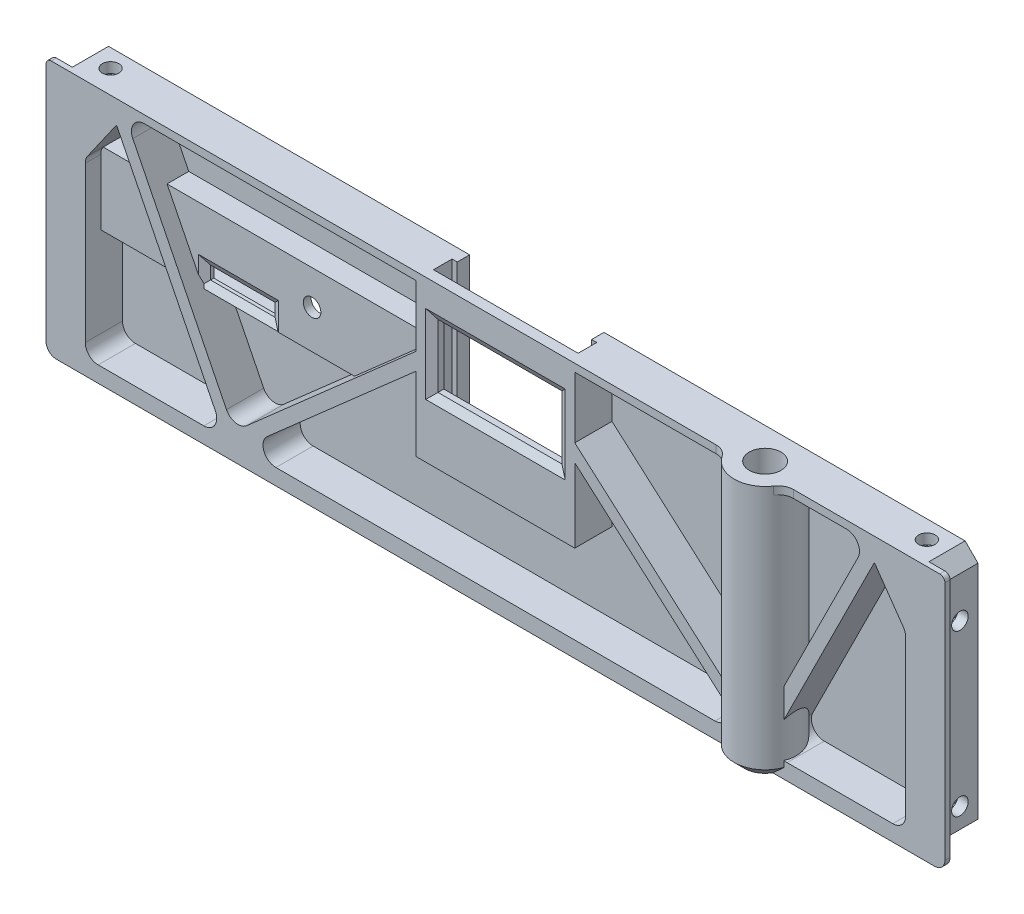
SolidWorks part; units mm, degrees
ref_plane "Front Plane" through (0, 0, 0) normal (0, 0, 1) x (1, 0, 0)
ref_plane "Top Plane" through (0, 0, 0) normal (0, 1, 0) x (1, 0, 0)
ref_plane "Right Plane" through (0, 0, 0) normal (1, 0, 0) x (0, 0, -1)
sketch "Sketch1" plane through (0, 0, 0) normal (0, 0, 1) x (1, 0, 0)
  line L1 (87, -25.55) -> (-87, -25.55)
  line L2 (87, -25.55) -> (87, 25.55)
  line L3 (87, 25.55) -> (-87, 25.55)
  line L4 (-87, -25.55) -> (-87, 25.55)
  line L5 (87, -25.55) -> (-87, 25.55) construction
  line L6 (87, 25.55) -> (-87, -25.55) construction
  point P0 (0, 0)
  dimension "D1" = 174
  dimension "D2" = 51.1
extrude "Boss-Extrude1" add sketch "Sketch1" against normal blind 8
sketch "Sketch2" plane through (0, 0, -8) normal (0, 0, -1) x (-1, 0, 0)
  line L5 (-87, -25.55) -> (-87, 25.55) construction
  line L6 (-87, 25.55) -> (87, 25.55) construction
  line L13 (85.4, -23.95) -> (85.4, 23.95)
  line L14 (-85.4, -23.95) -> (85.4, -23.95)
  line L15 (-85.4, 23.95) -> (-85.4, -23.95)
  line L16 (85.4, 23.95) -> (-85.4, 23.95)
  point P2 (0, 23.95)
  point P5 (85.4, 0)
  dimension "D1" = 1.6
  dimension "D2" = 1.6
extrude "Cut-Extrude1" cut sketch "Sketch2" against normal offset from surface (7 mm away) 1 flip side to cut up to face at (0, 0, 0)
chamfer "Chamfer1" distance 2.5 angle 45 4 edges at (-85.4, -23.95, -4.5) (-85.4, 23.95, -4.5) (85.4, -23.95, -4.5) (85.4, 23.95, -4.5)
fillet "Fillet1" radius 2 2 edges at (-87, -25.55, -0.5) (87, -25.55, -0.5)
sketch "Sketch3" plane through (0, 0, 0) normal (0, 0, 1) x (1, 0, 0)
  line L1 (-82.9, 23.95) -> (-85.4, 21.45) construction
  line L2 (-82.9, 23.95) -> (82.9, 23.95) construction
  line L3 (-82.9, 23.95) -> (-85.4, 21.45) construction
  line L4 (-82.9, 23.95) -> (82.9, 23.95) construction
  line L5 (85.4, 21.45) -> (82.9, 23.95) construction
  line L6 (85.4, 21.45) -> (85.4, -21.45) construction
  line L7 (82.9, -23.95) -> (85.4, -21.45) construction
  line L8 (82.9, -23.95) -> (-82.9, -23.95) construction
  line L9 (-85.4, -21.45) -> (-82.9, -23.95) construction
  line L10 (-85.4, -21.45) -> (-85.4, 21.45) construction
  line L11 (85.4, 21.45) -> (82.9, 23.95) construction
  line L12 (85.4, 21.45) -> (85.4, -21.45) construction
  line L13 (82.9, -23.95) -> (85.4, -21.45) construction
  line L14 (82.9, -23.95) -> (-82.9, -23.95) construction
  line L15 (-85.4, -21.45) -> (-82.9, -23.95) construction
  line L16 (-85.4, -21.45) -> (-85.4, 21.45) construction
  line L26 (79.4, -22.45) -> (-79.4, -22.45)
  line L27 (79.4, -22.45) -> (79.4, 22.45)
  line L28 (79.4, 22.45) -> (-79.4, 22.45)
  line L29 (-79.4, -22.45) -> (-79.4, 22.45)
  line L30 (79.4, -22.45) -> (-79.4, 22.45) construction
  line L31 (79.4, 22.45) -> (-79.4, -22.45) construction
  point P4 (0, 0)
  dimension "D1" = 3
  dimension "D2" = 6
extrude "Cut-Extrude2" cut sketch "Sketch3" against normal offset from surface (7.2 mm away) 0.8 up to face at (0, 0, -8)
sketch "Sketch9" plane through (0, 0, 0) normal (0, 0, 1) x (1, 0, 0)
  line L0 (-73.4, 22.45) -> (-73.4, 19.45)
  line L1 (-79.4, 22.45) -> (79.4, 22.45) construction
  line L2 (-73.4, 19.45) -> (-79.4, 10.8811)
  line L3 (-79.4, -22.45) -> (-79.4, 22.45) construction
  line L4 (-79.4, 10.8811) -> (-79.4, 22.45)
  line L5 (-79.4, 22.45) -> (-73.4, 22.45)
  dimension "D1" = 6
  dimension "D2" = 35
  dimension "D3" = 3
extrude "Boss-Extrude2" add sketch "Sketch9" against normal up to surface (7.2 mm away) up to face at (0, 0, -7.2)
hole_wizard "Ø3.0mm Dowel Hole1" positions "Sketch4" profile "Sketch5" hole size "Ø3.0" standard "ANSI Metric"
sketch "Sketch4" plane through (-85.4, 0, 0) normal (-1, 0, 0) x (0, 0, 1)
  line L0 (-4.5, 13.55) -> (-4.5, -17.55) construction
  line L2 (-8, -21.45) -> (-8, 21.45) construction
  line L4 (0, -25.55) -> (-1, -25.55) construction
  line L5 (-1, 25.55) -> (0, 25.55) construction
  point P0 (-4.5, 13.55)
  point P3 (-4.5, -17.55)
  dimension "D1" = 3.5
  dimension "D2" = 12
  dimension "D3" = 8
sketch "Sketch5" plane through (-85.4, 13.55, -4.5) normal (0, 1, 0) x (0, 0, 1)
  line L0 (0, 0) -> (0, 5)
  line L1 (0, 5) -> (1.6, 5)
  line L2 (1.6, 5) -> (1.6, 0)
  line L5 (1.6, 0) -> (0, 0)
  line L10 (0, 5) -> (-1.6, 5) construction
  line L11 (0, -6.35) -> (0, 107.95) construction
  dimension "Hole Dia." = 3.2
  dimension "Hole Depth" = 5
  dimension "Drill Angle" = 180
hole_wizard "Ø3.0mm Dowel Hole2" positions "Sketch7" profile "Sketch8" hole size "Ø3.0" standard "ANSI Metric"
sketch "Sketch7" plane through (0, 23.95, 0) normal (0, 1, 0) x (1, 0, 0)
  line L0 (-82.9, 8) -> (82.9, 8) construction
  line L2 (-87, 1) -> (-87, 0) construction
  point P0 (-79, 4.5)
  dimension "D1" = 3.5
  dimension "D2" = 8
sketch "Sketch8" plane through (-79, 23.95, -4.5) normal (1, 0, 0) x (0, 0, 1)
  line L0 (0, 0) -> (0, 5)
  line L1 (0, 5) -> (1.6, 5)
  line L2 (1.6, 5) -> (1.6, 0)
  line L5 (1.6, 0) -> (0, 0)
  line L10 (0, 5) -> (-1.6, 5) construction
  line L11 (0, -6.35) -> (0, 107.95) construction
  dimension "Hole Dia." = 3.2
  dimension "Hole Depth" = 5
  dimension "Drill Angle" = 180
sketch "Sketch10" plane through (-85.4, 0, 0) normal (-1, 0, 0) x (0, 0, 1)
  line L0 (-8, -21.45) -> (-8, 21.45) construction
  line L1 (-8, 16.3) -> (-1.75, 16.3)
  line L2 (-8, 16.3) -> (-8, 10.8)
  line L3 (-8, 10.8) -> (-1.75, 10.8)
  line L4 (-1.75, 16.3) -> (-1.75, 10.8)
  line L6 (-8, -14.8) -> (-1.75, -14.8)
  line L7 (-8, -14.8) -> (-8, -20.3)
  line L8 (-8, -20.3) -> (-1.75, -20.3)
  line L9 (-1.75, -14.8) -> (-1.75, -20.3)
  point P6 (-1.75, -17.55)
  point P8 (-1.75, 13.55)
  dimension "D1" = 5.5
  dimension "D2" = 2.75
extrude "Cut-Extrude3" cut sketch "Sketch10" against normal blind 1.8 from offset 2 offset against normal yes
sketch "Sketch11" plane through (0, 23.95, 0) normal (0, 1, 0) x (1, 0, 0)
  line L0 (-82.9, 8) -> (82.9, 8) construction
  line L1 (-81.75, 8) -> (-76.25, 8)
  line L2 (-81.75, 8) -> (-81.75, 1.75)
  line L3 (-81.75, 1.75) -> (-76.25, 1.75)
  line L4 (-76.25, 8) -> (-76.25, 1.75)
  point P6 (-79, 1.75)
  dimension "D1" = 5.5
  dimension "D2" = 2.75
extrude "Cut-Extrude4" cut sketch "Sketch11" against normal blind 1.8 from offset 2 offset against normal yes
mirror "Mirror1" about plane through (0, 0, 0) normal (1, 0, 0) of "Cut-Extrude4", "Cut-Extrude3", "Ø3.0mm Dowel Hole2", "Ø3.0mm Dowel Hole1", "Boss-Extrude2"
sketch "Sketch12" plane through (0, 0, -7.2) normal (0, 0, 1) x (1, 0, 0)
  line L0 (-73.4, 22.45) -> (-51.0137, -22.45) construction
  line L1 (-79.4, -22.45) -> (79.4, -22.45) construction
  line L2 (-51.0137, -22.45) -> (0, 22.45) construction
  line L3 (73.4, 22.45) -> (-73.4, 22.45) construction
  line L4 (0, 22.45) -> (51.0137, -22.45) construction
  line L5 (51.0137, -22.45) -> (73.4, 22.45) construction
  line L6 (-74.5187, 21.8923) -> (-51.9874, -23.2985)
  line L7 (-50.4317, -23.603) -> (0, 20.7848)
  line L8 (0, 20.7848) -> (50.4317, -23.603)
  line L9 (51.9874, -23.2985) -> (74.5187, 21.8923)
  line L10 (-72.2813, 23.0077) -> (-50.62, -20.4382)
  line L11 (-50.62, -20.4382) -> (-0.6607, 23.5337)
  line L12 (0.6607, 23.5337) -> (50.62, -20.4382)
  line L13 (50.62, -20.4382) -> (72.2813, 23.0077)
  line L14 (0, 20.7848) -> (51.4074, -24.4618) construction
  line L15 (51.4074, -24.4618) -> (74.5187, 21.8923) construction
  line L16 (-50.62, -20.4382) -> (0, 24.1152) construction
  line L17 (0, 24.1152) -> (50.62, -20.4382) construction
  line L18 (-74.5187, 21.8923) -> (-51.4074, -24.4618) construction
  line L19 (-51.4074, -24.4618) -> (0, 20.7848) construction
  line L20 (79.4, -22.45) -> (-79.4, -22.45) construction
  line L21 (-79.4, -22.45) -> (-79.4, 10.8811) construction
  arc A0 (-74.5187, 21.8923) -> (-72.2813, 23.0077) centre (-73.4, 22.45) cw
  arc A1 (74.5187, 21.8923) -> (72.2813, 23.0077) centre (73.4, 22.45) ccw
  arc A2 (50.4317, -23.603) -> (51.9874, -23.2985) centre (51.0924, -22.8524) ccw
  arc A3 (-0.6607, 23.5337) -> (0.6607, 23.5337) centre (0, 22.783) cw
  arc A4 (-51.9874, -23.2985) -> (-50.4317, -23.603) centre (-51.0924, -22.8524) ccw
  dimension "D3" = 1
  dimension "D1" = 1.25
  dimension "D2" = 26.5
extrude "Boss-Extrude3" add sketch "Sketch12" along normal up to surface (7.2 mm away) up to face at (0, 7.5828, 0)
sketch "Sketch13" plane through (0, 0, 0) normal (0, 0, 1) x (1, 0, 0)
  line L0 (-73.4, 19.45) -> (-73.4, 19.6486)
  line L1 (-73.4, 19.6486) -> (-73.301, 19.45)
  line L2 (-73.4, 19.6486) -> (-52.4104, -22.45) construction
  line L3 (-73.301, 19.45) -> (-73.4, 19.45)
  line L4 (0, 0) -> (0, 25.4565) construction
  line L5 (73.301, 19.45) -> (73.4, 19.45)
  line L6 (73.4, 19.6486) -> (73.301, 19.45)
  line L7 (73.4, 19.45) -> (73.4, 19.6486)
extrude "Small Fix" add sketch "Sketch13" against normal up to surface (7.2 mm away) up to face at (-71.6021, 1.0159, -7.2)
fillet "Fillet2" radius 2.5 15 edges at (79.4, -22.45, -3.6) (79.4, 10.8811, -3.6) (52.4104, -22.45, -3.6) (72.0032, 22.45, -3.6) (50.62, -20.4382, -3.6) (1.892, 22.45, -3.6) (49.1217, -22.45, -3.6) (0, 20.7848, -3.6) (-49.1217, -22.45, -3.6) (-1.892, 22.45, -3.6) (-50.62, -20.4382, -3.6) (-72.0032, 22.45, -3.6) (-79.4, 10.8811, -3.6) (-79.4, -22.45, -3.6) (-52.4104, -22.45, -3.6)
fillet "Fillet3" radius 0.1 4 edges at (73.4, 19.45, -3.6) (73.301, 19.45, -3.6) (-73.301, 19.45, -3.6) (-73.4, 19.45, -3.6)
sketch "Sketch14" plane through (0, 0, -8) normal (0, 0, -1) x (-1, 0, 0)
  line L1 (-13.85, 22.45) -> (13.85, 22.45) construction
  line L2 (-13.85, 22.45) -> (-13.85, -5.55) construction
  line L3 (-13.85, -5.55) -> (13.85, -5.55) construction
  line L4 (13.85, 22.45) -> (13.85, -5.55) construction
  line L5 (82.9, 23.95) -> (-82.9, 23.95) construction
  line L6 (-15.35, 23.95) -> (-15.35, -7.05)
  line L7 (-15.35, -7.05) -> (15.35, -7.05)
  line L8 (15.35, 23.95) -> (15.35, -7.05)
  line L9 (-15.35, 22.45) -> (-15.35, -7.05) construction
  line L10 (15.35, 22.45) -> (15.35, -7.05) construction
  line L11 (-15.35, 23.95) -> (15.35, 23.95)
  point P6 (0, -5.55)
  dimension "D1" = 28
  dimension "D2" = 27.7
  dimension "D3" = 1.5
  dimension "D4" = 1.5
extrude "Boss-Extrude4" add sketch "Sketch14" against normal up to surface (8 mm away) up to face at (-42.2461, 7.7039, 0)
sketch "Sketch17" plane through (0, 23.95, 0) normal (0, 1, 0) x (1, 0, 0)
  line L0 (87, 0) -> (-87, 0) construction
  line L1 (-14, 5.6) -> (14, 5.6)
  line L2 (-14, 5.6) -> (-14, 2)
  line L3 (-14, 2) -> (14, 2)
  line L4 (14, 5.6) -> (14, 2)
  point P8 (0, 2)
  point P11 (-13.85, 8)
  dimension "D1" = 3.6
  dimension "D2" = 2
  dimension "D3" = 0.15
extrude "Cut-Extrude6" cut sketch "Sketch17" against normal up to vertex (29.5 mm away) up to point (13.85, -5.55, -8)
sketch "Sketch18" plane through (0, 0, -8) normal (0, 0, -1) x (-1, 0, 0)
  line L0 (82.9, 23.95) -> (-82.9, 23.95) construction
  line L1 (-13, 23.95) -> (13, 23.95)
  line L2 (-13, 23.95) -> (-13, -2.55)
  line L3 (-13, -2.55) -> (13, -2.55)
  line L4 (13, 23.95) -> (13, -2.55)
  line L5 (-14, -5.55) -> (14, -5.55) construction
  point P6 (0, -2.55)
  dimension "D1" = 26
  dimension "D2" = 3
extrude "Cut-Extrude7" cut sketch "Sketch18" against normal up to surface (6 mm away) up to face at (0, 9.2, -2)
sketch "Sketch19" plane through (0, 0, 0) normal (0, 0, 1) x (1, 0, 0)
  line L1 (-13, 18.2) -> (13, 18.2) construction
  line L2 (-13, 18.2) -> (-13, 3.95) construction
  line L3 (-13, 3.95) -> (13, 3.95) construction
  line L4 (13, 18.2) -> (13, 3.95) construction
  line L6 (-12, 17.2) -> (12, 17.2)
  line L7 (12, 17.2) -> (12, 4.95)
  line L8 (-12, 4.95) -> (12, 4.95)
  line L9 (-12, 17.2) -> (-12, 4.95)
  dimension "D1" = 1
extrude "Cut-Extrude8" cut sketch "Sketch19" against normal up to surface (2 mm away) up to face at (0, 9.2, -2)
chamfer "Chamfer2" distance 1.5 angle 30 4 edges at (0, 4.95, 0) (-12, 11.075, 0) (12, 11.075, 0) (0, 17.2, 0) first distance on face at (0, 11.075, 0)
sketch "Sketch21" plane through (0, 0, -1) normal (0, 0, -1) x (-1, 0, 0)
  line L0 (87, -23.55) -> (87, 25.55) construction
  line L1 (-87, 25.55) -> (87, 25.55)
  line L2 (-87, 25.55) -> (-87, 23.95)
  line L3 (-87, 23.95) -> (87, 23.95)
  line L4 (87, 25.55) -> (87, 23.95)
  line L5 (82.9, 23.95) -> (-82.9, 23.95) construction
extrude "Cut-Extrude10" cut sketch "Sketch21" against normal through all
sketch "Sketch22" plane through (0, 0, 0) normal (0, 0, 1) x (1, 0, 0)
  line L0 (-79.4, -2.55) -> (-30.296, -2.55)
  line L1 (-79.4, -2.55) -> (-79.4, 11.55)
  line L2 (-79.4, 11.55) -> (-23.6, 11.55)
  line L3 (-23.6, 3.3435) -> (-23.6, 11.55) construction
  line L4 (-81.6, 0.95) -> (-25.6, 0.95) construction
  line L5 (-81.6, 0.95) -> (-81.6, 2.55) construction
  line L6 (-81.6, 2.55) -> (-25.6, 2.55) construction
  line L7 (-25.6, 0.95) -> (-25.6, 2.55) construction
  line L9 (-30.296, -2.55) -> (-15.35, 10.6048)
  line L10 (-15.35, 11.55) -> (-23.6, 11.55)
  line L12 (-15.35, 10.6048) -> (-48.1808, -18.2914) construction
  line L14 (-79.4, 10.0929) -> (-79.4, -19.95) construction
  line L15 (82.9, -23.95) -> (-82.9, -23.95) construction
  line L16 (-87, 23.95) -> (-87, -23.55) construction
  line L17 (-15.35, 10.6048) -> (-15.35, 11.55)
  line L18 (-15.35, 22.45) -> (-15.35, 10.6048) construction
  line L19 (-15.35, 10.6048) -> (-48.1808, -18.2914) construction
  dimension "D1" = 9
  dimension "D2" = 2
  dimension "D3" = 56
  dimension "D4" = 1.6
  dimension "D5" = 24.9
  dimension "D6" = 5.4
  dimension "D7" = 3.5
extrude "Boss-Extrude5" add sketch "Sketch22" against normal up to surface (7.2 mm away) from offset 3 up to face at (-71.6654, -0.5445, -7.2) offset against normal yes
sketch "Sketch23" plane through (0, 0, -8) normal (0, 0, -1) x (-1, 0, 0)
  line L1 (24.1, 10.55) -> (83.1, 10.55)
  line L2 (24.1, 10.55) -> (24.1, 0.95)
  line L3 (24.1, 0.95) -> (83.1, 0.95)
  line L4 (83.1, 10.55) -> (83.1, 0.95)
  line L5 (81.6, 0.95) -> (25.6, 0.95) construction
  line L6 (81.6, 0.95) -> (81.6, 2.55) construction
  line L7 (79.4, 11.55) -> (23.6, 11.55) construction
  point P6 (53.6, 0.95)
  point P7 (53.6, 0.95)
  dimension "D1" = 1.5
  dimension "D2" = 1
extrude "Cut-Extrude11" cut sketch "Sketch23" against normal offset from surface (3.5 mm away) 1.5 up to face at (-74.7474, 6.6091, -3)
sketch "Sketch25" plane through (0, 0, -8) normal (0, 0, -1) x (-1, 0, 0)
  line L0 (24.1, 0.95) -> (83.1, 0.95) construction
  line L1 (32.1, 0.95) -> (67.1, 0.95)
  line L2 (32.1, 0.95) -> (32.1, -1.55)
  line L3 (32.1, -1.55) -> (67.1, -1.55)
  line L4 (67.1, 0.95) -> (67.1, -1.55)
  line L5 (24.1, 10.55) -> (24.1, 0.95) construction
  line L6 (83.1, 10.55) -> (83.1, 0.95) construction
  dimension "D1" = 8
  dimension "D2" = 16
  dimension "D3" = 2.5
extrude "Cut-Extrude12" cut sketch "Sketch25" against normal up to surface (3.5 mm away) up to face at (-53.6, 5.75, -4.5)
sketch "Sketch26" plane through (0, 0, -8) normal (0, 0, -1) x (-1, 0, 0)
  line L0 (32.1, 0.95) -> (24.1, 0.95) construction
  line L1 (24.1, 10.55) -> (29.1, 10.55)
  line L2 (24.1, 10.55) -> (24.1, 3.15)
  line L3 (24.1, 3.15) -> (29.1, 3.15)
  line L4 (29.1, 10.55) -> (29.1, 3.15)
  line L5 (83.1, 10.55) -> (76.1, 10.55)
  line L6 (83.1, 10.55) -> (83.1, 3.15)
  line L7 (83.1, 3.15) -> (76.1, 3.15)
  line L8 (76.1, 10.55) -> (76.1, 3.15)
  dimension "D1" = 5
  dimension "D2" = 7
  dimension "D3" = 2.2
extrude "Boss-Extrude6" add sketch "Sketch26" against normal up to surface (3.5 mm away) up to face at (-51.6, 2.725, -4.5)
sketch "Sketch27" plane through (0, 0, -3) normal (0, 0, 1) x (1, 0, 0)
  line L0 (-47.2737, 0.435) -> (-47.2737, -0.365) construction
  line L1 (-58.2737, 0.535) -> (-47.2737, 0.535) construction
  line L2 (-58.2737, 0.535) -> (-58.2737, -0.465) construction
  line L3 (-58.2737, -0.465) -> (-47.2737, -0.465) construction
  line L4 (-47.2737, 0.535) -> (-47.2737, -0.465) construction
  line L5 (-58.2737, -0.365) -> (-58.2737, 0.435) construction
  line L8 (-57.7737, 0.535) -> (-47.7737, 0.535) construction
  line L9 (-47.7737, -0.465) -> (-57.7737, -0.465) construction
  line L10 (-59.0237, 1.285) -> (-46.5237, 1.285)
  line L11 (-46.5237, 1.285) -> (-46.5237, -1.215)
  line L12 (-59.0237, -1.215) -> (-46.5237, -1.215)
  line L13 (-59.0237, 1.285) -> (-59.0237, -1.215)
  circle A0 centre (-38.5, 4.9) radius 1.2 construction
  arc A1 (-38.5, 6.1) -> (-38.5, 3.7) centre (-38.5, 4.9) ccw construction
  circle A2 centre (-38.5, 4.9) radius 1.7
  dimension "D1" = 0.75
  dimension "D2" = 0.5
extrude "Cut-Extrude13" cut sketch "Sketch27" against normal up to surface (1.5 mm away) up to face at (-51.9333, 2.8667, -4.5)
fillet "Fillet4" radius 1 2 edges at (87, 23.95, -0.5) (-87, 23.95, -0.5)
sketch "Sketch29" plane through (0, 23.95, 0) normal (0, 1, 0) x (1, 0, 0)
  line L0 (50.195, 8) -> (50.195, 0) construction
  line L1 (13, 8) -> (82.9, 8) construction
  line L2 (86, 0) -> (-86, 0) construction
  circle A0 centre (50.195, 2) radius 3 construction
  circle A1 centre (50.195, 2) radius 6
  dimension "D1" = 6
  dimension "D2" = 12
extrude "Boss-Extrude8" add sketch "Sketch29" against normal up to surface (49.5 mm away) up to face at (0, -25.55, -0.5)
sketch "Sketch30" plane through (0, 23.95, 0) normal (0, 1, 0) x (1, 0, 0)
  circle A0 centre (50.195, 2) radius 3 construction
  circle A1 centre (50.195, 2) radius 3 construction
  circle A2 centre (50.195, 2) radius 3.075
  dimension "D1" = 6.15
extrude "Cut-Extrude14" cut sketch "Sketch30" against normal offset from surface (43.9 mm away) 4 up to face at (-18.2377, -23.95, -4.8432)
sketch "Sketch31" plane through (0, -23.95, 0) normal (0, -1, 0) x (1, 0, 0)
  line L0 (44.2789, -1) -> (-82.9, -1) construction
  line L1 (44.195, -1) -> (56.195, -1)
  line L2 (44.195, -1) -> (44.195, -8)
  line L3 (44.195, -8) -> (56.195, -8)
  line L4 (56.195, -1) -> (56.195, -8)
  line L5 (82.9, -8) -> (50.195, -8) construction
  circle A0 centre (50.195, -2) radius 6 construction
extrude "Cut-Extrude15" cut sketch "Sketch31" along normal up to surface (1.6 mm away) up to face at (25.0975, -25.55, -0.875)
chamfer "Chamfer3" distance 2 angle 45 1 edges at (50.195, -25.55, 4)
fillet "Fillet5" radius 3 2 edges at (55.8519, 23.2, 0) (44.5381, 23.2, 0)
sketch "Sketch32" plane through (0, 0, -1.75) normal (0, 0, -1) x (-1, 0, 0)
  line L1 (-81.75, 21.95) -> (-76.25, 21.95)
  line L2 (-81.75, 21.95) -> (-81.75, 20.15)
  line L3 (-81.75, 20.15) -> (-76.25, 20.15)
  line L4 (-76.25, 21.95) -> (-76.25, 20.15)
  line L5 (-83.4, 16.3) -> (-81.6, 16.3)
  line L6 (-83.4, 16.3) -> (-83.4, 10.8)
  line L7 (-83.4, 10.8) -> (-81.6, 10.8)
  line L8 (-81.6, 16.3) -> (-81.6, 10.8)
  line L9 (-83.4, -14.8) -> (-81.6, -14.8)
  line L10 (-83.4, -14.8) -> (-83.4, -20.3)
  line L11 (-83.4, -20.3) -> (-81.6, -20.3)
  line L12 (-81.6, -14.8) -> (-81.6, -20.3)
  line L13 (76.25, 21.95) -> (81.75, 21.95)
  line L14 (76.25, 21.95) -> (76.25, 20.15)
  line L15 (76.25, 20.15) -> (81.75, 20.15)
  line L16 (81.75, 21.95) -> (81.75, 20.15)
  line L17 (81.6, 16.3) -> (83.4, 16.3)
  line L18 (81.6, 16.3) -> (81.6, 10.8)
  line L19 (81.6, 10.8) -> (83.4, 10.8)
  line L20 (83.4, 16.3) -> (83.4, 10.8)
  line L21 (81.6, -14.8) -> (83.4, -14.8)
  line L22 (81.6, -14.8) -> (81.6, -20.3)
  line L23 (81.6, -20.3) -> (83.4, -20.3)
  line L24 (83.4, -14.8) -> (83.4, -20.3)
extrude "Cut-Extrude17" cut sketch "Sketch32" against normal blind 0.1
chamfer "Chamfer4" distance 1.5 angle 30 4 edges at (-46.5237, 0.035, -3) (-52.7737, -1.215, -3) (-59.0237, 0.035, -3) (-52.7737, 1.285, -3) first distance on face at (-52.7737, 0.035, -3)
